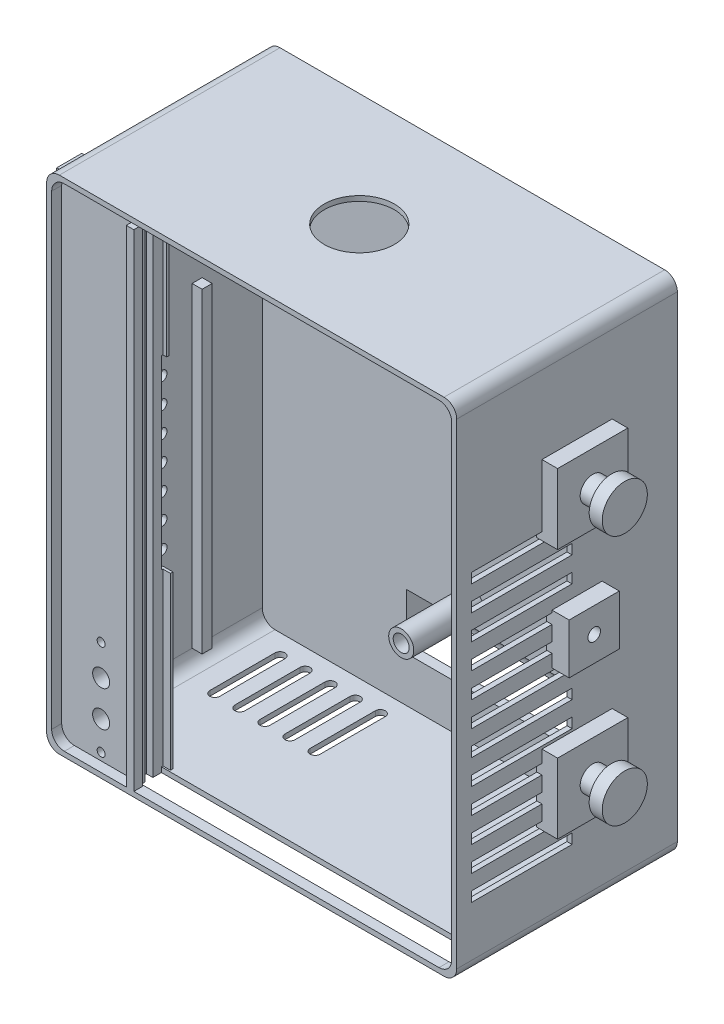
SolidWorks part; units mm, degrees
material "PVC 0.007 Plasticized"
ref_plane "Front Plane" through (0, 0, 0) normal (0, 0, 1) x (1, 0, 0)
ref_plane "Top Plane" through (0, 0, 0) normal (0, 1, 0) x (1, 0, 0)
ref_plane "Right Plane" through (0, 0, 0) normal (1, 0, 0) x (0, 0, -1)
sketch "Sketch1" plane through (0, 0, 0) normal (0, 0, 1) x (1, 0, 0)
  line L1 (-38.35, 50) -> (38.35, 50)
  line L2 (-40.88, 47.47) -> (-40.88, -47.47)
  line L3 (-38.35, -50) -> (38.35, -50)
  line L4 (40.88, 47.47) -> (40.88, -47.47)
  line L5 (-40.88, 50) -> (40.88, -50) construction
  line L6 (-40.88, -50) -> (40.88, 50) construction
  arc A0 (38.35, 50) -> (40.88, 47.47) centre (38.35, 47.47) cw
  arc A1 (40.88, -47.47) -> (38.35, -50) centre (38.35, -47.47) cw
  arc A2 (-40.88, -47.47) -> (-38.35, -50) centre (-38.35, -47.47) ccw
  arc A3 (-40.88, 47.47) -> (-38.35, 50) centre (-38.35, 47.47) cw
  point P0 (0, 0)
  dimension "D3" = 2.53
  dimension "D1" = 81.76
  dimension "D2" = 100
extrude "Boss-Extrude1" add sketch "Sketch1" along normal blind 44
sketch "Sketch2" plane through (0, 0, 44) normal (0, 0, 1) x (1, 0, 0)
  line L0 (38.35, 50) -> (-38.35, 50) construction
  line L1 (-37.35, 49) -> (37.35, 49)
  line L2 (-39.88, 46.47) -> (-39.88, -46.47)
  line L3 (-37.35, -49) -> (37.35, -49)
  line L4 (39.88, 46.47) -> (39.88, -46.47)
  line L5 (-39.88, 49) -> (39.88, -49) construction
  line L6 (-39.88, -49) -> (39.88, 49) construction
  line L7 (-40.88, 47.47) -> (-40.88, -47.47) construction
  arc A0 (37.35, 49) -> (39.88, 46.47) centre (37.35, 46.47) cw
  arc A1 (39.88, -46.47) -> (37.35, -49) centre (37.35, -46.47) cw
  arc A2 (-39.88, -46.47) -> (-37.35, -49) centre (-37.35, -46.47) ccw
  arc A3 (-39.88, 46.47) -> (-37.35, 49) centre (-37.35, 46.47) cw
  point P0 (0, 0)
  dimension "D3" = 2.53
  dimension "D1" = 1
  dimension "D2" = 1
extrude "Cut-Extrude1" cut sketch "Sketch2" against normal blind 42
sketch "Sketch3" plane through (-39.88, 0, 0) normal (1, 0, 0) x (0, 0, -1)
  line L0 (-16, 16.53) -> (-14, 16.53)
  line L2 (-14, 16.53) -> (-14, -46.47)
  line L4 (-16, 16.53) -> (-16, -46.47)
  line L6 (0, -47.47) -> (0, 47.47) construction
  line L9 (-2, -46.47) -> (-44, -46.47) construction
  line L10 (-14, -46.47) -> (-16, -46.47)
  dimension "D1" = 14
  dimension "D2" = 2
  dimension "D3" = 63
extrude "Boss-Extrude2" add sketch "Sketch3" along normal blind 2
sketch "Sketch7" plane through (0, 0, 0) normal (0, 0, -1) x (-1, 0, 0)
  line L7 (38.35, -50) -> (-38.35, -50) construction
  line L8 (-30.88, 15) -> (14.12, 15)
  line L9 (-30.88, 15) -> (-30.88, -40)
  line L10 (-30.88, -40) -> (14.12, -40)
  line L12 (14.12, 15) -> (14.12, -40)
  line L13 (-40.88, -47.47) -> (-40.88, 47.47) construction
  dimension "D2" = 45
  dimension "D3" = 10
  dimension "D1" = 55
  dimension "D4" = 10
extrude "Boss-Extrude5" add sketch "Sketch7" along normal blind 10 contours L12 L10 L9 L8
sketch "Sketch20" plane through (0, 15, 0) normal (0, 1, 0) x (1, 0, 0)
  line L0 (30.88, 0) -> (-14.12, 0) construction
  line L1 (-11.12, 0) -> (27.88, 0)
  line L2 (-11.12, 0) -> (-11.12, 7)
  line L3 (-11.12, 7) -> (27.88, 7)
  line L4 (27.88, 0) -> (27.88, 7)
  line L5 (30.88, 10) -> (-14.12, 10) construction
  line L6 (30.88, 10) -> (30.88, 0) construction
  line L7 (-14.12, 10) -> (-14.12, 0) construction
  point P10 (30.88, 5)
  dimension "D1" = 3
  dimension "D2" = 3
  dimension "D3" = 3
sketch "Sketch21" plane through (0, -40, 0) normal (0, -1, 0) x (1, 0, 0)
  line L0 (27.88, 0) -> (27.88, -7) construction
  line L1 (-11.12, 0) -> (27.88, 0) construction
  line L2 (-11.12, 0) -> (-11.12, -7) construction
  line L3 (-11.12, -7) -> (27.88, -7) construction
  line L4 (27.88, 0) -> (27.88, -7)
  line L5 (-11.12, 0) -> (27.88, 0)
  line L6 (-11.12, 0) -> (-11.12, -7)
  line L7 (-11.12, -7) -> (27.88, -7)
extrude "Cut-Extrude12" cut sketch "Sketch21" against normal blind 52
sketch "Sketch22" plane through (30.88, 0, 0) normal (1, 0, 0) x (0, 0, -1)
  line L0 (10, -40) -> (0, -40) construction
  circle A0 centre (5, -40) radius 3
  dimension "D1" = 6
extrude "Cut-Extrude13" cut sketch "Sketch22" against normal through all
sketch "Sketch23" plane through (0, 0, -10) normal (0, 0, -1) x (-1, 0, 0)
  line L1 (-27.88, -40) -> (11.12, -40)
  line L3 (-27.88, -30) -> (11.12, -30)
  line L5 (-27.88, -30) -> (-27.88, -40)
  line L6 (11.12, -40) -> (11.12, -30)
  line L8 (14.12, 15) -> (14.12, -40) construction
  dimension "D1" = 3
  dimension "D2" = 10
extrude "Cut-Extrude19" cut sketch "Sketch23" against normal through all from offset 10 contours L3 L6 L1 L5 offset against normal yes
sketch "Sketch25" plane through (0, 0, 2) normal (0, 0, 1) x (1, 0, 0)
  line L1 (-11.12, -30) -> (27.88, -30)
  line L2 (-11.12, -30) -> (-11.12, -28.929)
  line L3 (-11.12, -28.929) -> (27.88, -28.929)
  line L4 (27.88, -30) -> (27.88, -28.929)
extrude "Cut-Extrude20" cut sketch "Sketch25" against normal up to next
fillet "Fillet1" radius 1 5 edges at (-12.62, -40, 0) (29.38, -40, 0) (-14.12, -12.5, 0) (30.88, -12.5, 0) (8.38, 15, 0)
sketch "Sketch27" plane through (0, -50, 0) normal (0, -1, 0) x (1, 0, 0)
  line L0 (-38.35, 0) -> (38.35, 0) construction
  line L1 (-33.35, 20) -> (-31.35, 20)
  line L2 (-33.35, 20) -> (-33.35, 5)
  line L3 (-33.35, 5) -> (-31.35, 5)
  line L4 (-31.35, 20) -> (-31.35, 5)
  line L5 (-38.35, 44) -> (-38.35, 0) construction
  dimension "D1" = 2
  dimension "D2" = 15
  dimension "D3" = 5
  dimension "D4" = 5
extrude "Cut-Extrude21" cut sketch "Sketch27" against normal up to next
fillet "Fillet2" 2 edges at (-33.35, -49.5, 20) (-31.35, -49.5, 20) type full round first side face at (-33.35, -49.5, 12.5) second side face at (-31.35, -49.5, 12.5) middle face at (-32.35, -49.5, 20)
fillet "Fillet3" 2 edges at (-31.35, -49.5, 5) (-33.35, -49.5, 5) type full round first side face at (-31.35, -49.5, 12) second side face at (-33.35, -49.5, 12) middle face at (-32.35, -49.5, 5)
sketch "Sketch28" plane through (-40.88, 0, 0) normal (-1, 0, 0) x (0, 0, 1)
  line L0 (44, 47.47) -> (44, -47.47) construction
  line L1 (21, -35.47) -> (41, -35.47)
  line L2 (21, -35.47) -> (21, -37.47)
  line L3 (21, -37.47) -> (41, -37.47)
  line L4 (41, -35.47) -> (41, -37.47)
  line L5 (44, -47.47) -> (0, -47.47) construction
  dimension "D1" = 3
  dimension "D2" = 20
  dimension "D3" = 10
  dimension "D4" = 2
extrude "Cut-Extrude22" cut sketch "Sketch28" against normal through all
fillet "Fillet4" 2 edges at (-40.38, -35.47, 21) (-40.38, -37.47, 21) type full round first side face at (-40.38, -35.47, 31) second side face at (-40.38, -37.47, 31) middle face at (-40.38, -36.47, 21)
fillet "Fillet5" 2 edges at (-40.38, -35.47, 41) (-40.38, -37.47, 41) type full round first side face at (-40.38, -35.47, 31.5) second side face at (-40.38, -37.47, 31.5) middle face at (-40.38, -36.47, 41)
pattern_linear "LPattern3" count 12 spacing 5 along (0, 1, 0) of "Fillet4", "Cut-Extrude22", "Fillet5"
ref_plane "Plane1" through (0, 0, 22) normal (0, 0, 1) x (1, 0, 0)
sketch "Sketch31" plane through (0, 49, 0) normal (0, -1, 0) x (1, 0, 0)
  line L0 (-51.7532, 22) -> (52.5033, 22) construction
  line L2 (-38.35, 44) -> (38.35, 44) construction
  line L4 (0, 49.6269) -> (0, -16.4709) construction
  circle A1 centre (0.0336, 22.5732) radius 4
  dimension "D1" = 22
  dimension "D2" = 8
extrude "Cut-Extrude23" cut sketch "Sketch31" against normal up to next contours A1
pattern_linear "LPattern2" count 5 spacing 5 along (1, 0, 0) of "Fillet3", "Fillet2", "Cut-Extrude21"
sketch "Sketch37" plane through (0, 0, 2) normal (0, 0, 1) x (1, 0, 0)
  circle A0 centre (1.8221, -24.7483) radius 1.6
  circle A1 centre (1.8221, -24.7483) radius 2.5
  dimension "D1" = 5
  dimension "D4" = 3.2
extrude "Boss-Extrude11" add sketch "Sketch37" along normal up to surface (14 mm away) up to face at (-38.88, -14.97, 16)
sketch "Sketch38" plane through (0, -50, 0) normal (0, -1, 0) x (1, 0, 0)
  line L0 (-38.35, 44) -> (-38.35, 0) construction
  line L1 (-38.35, 42) -> (38.35, 42)
  line L2 (-38.35, 42) -> (-38.35, 37)
  line L3 (-38.35, 37) -> (38.35, 37)
  line L4 (38.35, 42) -> (38.35, 37)
  line L5 (38.35, 44) -> (38.35, 0) construction
  line L7 (-38.35, 44) -> (38.35, 44) construction
  dimension "D1" = 5
  dimension "D2" = 2
extrude "Cut-Extrude25" cut sketch "Sketch38" against normal up to surface (99 mm away) up to face at (0.0336, 49, 18.5732)
sketch "Sketch39" plane through (0, 50, 0) normal (0, 1, 0) x (1, 0, 0)
  circle A0 centre (0.0336, -22.5732) radius 7
  dimension "D1" = 14
extrude "Cut-Extrude26" cut sketch "Sketch39" against normal up to next
sketch "Sketch40" plane through (0, 49, 0) normal (0, -1, 0) x (1, 0, 0)
  line L0 (38.35, 37) -> (38.35, 42) construction
  line L1 (38.35, 38.9347) -> (35.85, 38.9347)
  line L2 (38.35, 38.9347) -> (38.35, 40.9347)
  line L3 (38.35, 40.9347) -> (35.85, 40.9347)
  line L4 (35.85, 38.9347) -> (35.85, 40.9347)
  dimension "D1" = 2
  dimension "D2" = 2.5
extrude "Boss-Extrude12" add sketch "Sketch40" along normal up to surface (99 mm away) up to face at (-32.35, -50, 12.5)
chamfer "Chamfer1" distance 1 angle 45 1 edges at (35.85, -0.5, 40.9347)
chamfer "Chamfer2" distance 1 angle 45 1 edges at (35.85, -0.5, 38.9347)
fillet "Fillet6" radius 1 2 edges at (37.6, 49, 38.9347) (37.6, 49, 40.9347)
mirror "Mirror1" about plane through (0, 0, 0) normal (1, 0, 0) of "Fillet6", "Chamfer2", "Chamfer1", "Boss-Extrude12"
sketch "Sketch41" plane through (0, 0, 0) normal (0, 0, 1) x (1, 0, 0)
  line L0 (37.35, 49) -> (-37.35, 49) construction
  line L1 (-40.88, -50) -> (-25, -50)
  line L2 (-40.88, -50) -> (-40.88, 49)
  line L3 (-40.88, 49) -> (-25, 49)
  line L4 (-25, -50) -> (-25, 49)
extrude "Fixed_button_strip" add sketch "Sketch41" along normal blind 5 from offset 37
sketch "Sketch42" plane through (0, 0, 0) normal (0, 0, 1) x (1, 0, 0)
  circle A0 centre (-32.0187, -41.7454) radius 1.7
  circle A1 centre (-32.0187, -34.6434) radius 1.7
extrude "Plunger_guide_holes_D3p4" cut sketch "Sketch42" along normal blind 8 from offset 36
sketch "Sketch43" plane through (0, 0, 0) normal (0, 0, 1) x (1, 0, 0)
  circle A0 centre (-32.0187, -47.5) radius 0.8
  circle A1 centre (-32.0187, -28.5) radius 0.8
extrude "Retainer_pilot_holes_D1p6" cut sketch "Sketch43" along normal blind 8 from offset 35
sketch "Sketch44" plane through (0, 0, 0) normal (0, 0, 1) x (1, 0, 0)
  line L1 (-25, -49) -> (-23.5, -49)
  line L2 (-25, -49) -> (-25, 48)
  line L3 (-25, 48) -> (-23.5, 48)
  line L4 (-23.5, -49) -> (-23.5, 48)
extrude "New_door_outer_guide" add sketch "Sketch44" along normal blind 1.7 from offset 42.3
sketch "Sketch45" plane through (0, 0, 0) normal (0, 0, 1) x (1, 0, 0)
  line L0 (-23.5, -49) -> (-23.5, 48) construction
  line L1 (-25, -49) -> (-23.5, -49)
  line L2 (-25, -49) -> (-25, -15)
  line L3 (-25, -15) -> (-23.5, -15)
  line L4 (-23.5, -49) -> (-23.5, -15)
  line L5 (-25, -49) -> (-25, 49) construction
  line L6 (-25, 22) -> (-24.25, 22)
  line L7 (-25, 22) -> (-25, 48)
  line L8 (-25, 48) -> (-24.25, 48)
  line L9 (-24.25, 22) -> (-24.25, 48)
extrude "New_door_inner_guide_clear_of_PCB" add sketch "Sketch45" along normal blind 0.5 from offset 36.2
sketch "Sketch47" plane through (0, 0, 0) normal (0, 0, 1) x (1, 0, 0)
  line L0 (-25.5, -49) -> (-25, -49)
  line L1 (-25, -49) -> (-25, -15)
  line L2 (-25, -15) -> (-25.5, -15)
  line L3 (-25.5, -15) -> (-25.5, -49)
  line L4 (-25.5, 22) -> (-25, 22)
  line L5 (-25, 22) -> (-25, 48)
  line L6 (-25, 48) -> (-25.5, 48)
  line L7 (-25.5, 48) -> (-25.5, 22)
extrude "Join_inner_guide_to_fixed_strip" add sketch "Sketch47" along normal blind 1 from offset 36.2
sketch "Sketch48" plane through (0, 0, 0) normal (0, 0, 1) x (1, 0, 0)
  line L0 (-26.3, -50.5) -> (-24.7, -50.5)
  line L1 (-24.7, -50.5) -> (-24.7, 49.5)
  line L2 (-24.7, 49.5) -> (-26.3, 49.5)
  line L3 (-26.3, 49.5) -> (-26.3, -50.5)
extrude "Dust_overlap_rebate" cut sketch "Sketch48" along normal blind 1.6 from offset 38.7
sketch "Sketch52" plane through (0, 0, 0) normal (1, 0, 0) x (0, 0, -1)
  line L0 (-27, -32) -> (-13, -32)
  line L1 (-13, -32) -> (-13, -18)
  line L2 (-13, -18) -> (-27, -18)
  line L3 (-27, -18) -> (-27, -32)
  line L4 (-27, 18) -> (-13, 18)
  line L5 (-13, 18) -> (-13, 32)
  line L6 (-13, 32) -> (-27, 32)
  line L7 (-27, 32) -> (-27, 18)
extrude "Side_hanger_reinforced_pads" add sketch "Sketch52" along normal blind 4.2 from offset 39.8
sketch "Sketch53" plane through (0, 0, 0) normal (1, 0, 0) x (0, 0, -1)
  circle A0 centre (-20, -25) radius 2.5
  circle A1 centre (-20, 25) radius 2.5
extrude "Side_hanger_peg_necks_D5" add sketch "Sketch53" along normal blind 4 from offset 43.8
sketch "Sketch54" plane through (0, 0, 0) normal (1, 0, 0) x (0, 0, -1)
  circle A0 centre (-20, -25) radius 4.5
  circle A1 centre (-20, 25) radius 4.5
extrude "Side_hanger_retaining_heads_D9" add sketch "Sketch54" along normal blind 2.6 from offset 47.8
sketch "Sketch55" plane through (0, 0, 0) normal (1, 0, 0) x (0, 0, -1)
  line L0 (-25, -5) -> (-15, -5)
  line L1 (-15, -5) -> (-15, 5)
  line L2 (-15, 5) -> (-25, 5)
  line L3 (-25, 5) -> (-25, -5)
extrude "Side_hanger_lock_pad" add sketch "Sketch55" along normal blind 4.5 from offset 39.8
sketch "Sketch56" plane through (0, 0, 0) normal (1, 0, 0) x (0, 0, -1)
  circle A0 centre (-20, 0) radius 1.25
extrude "Side_hanger_M3_lock_pilot" cut sketch "Sketch56" along normal blind 6 from offset 39
